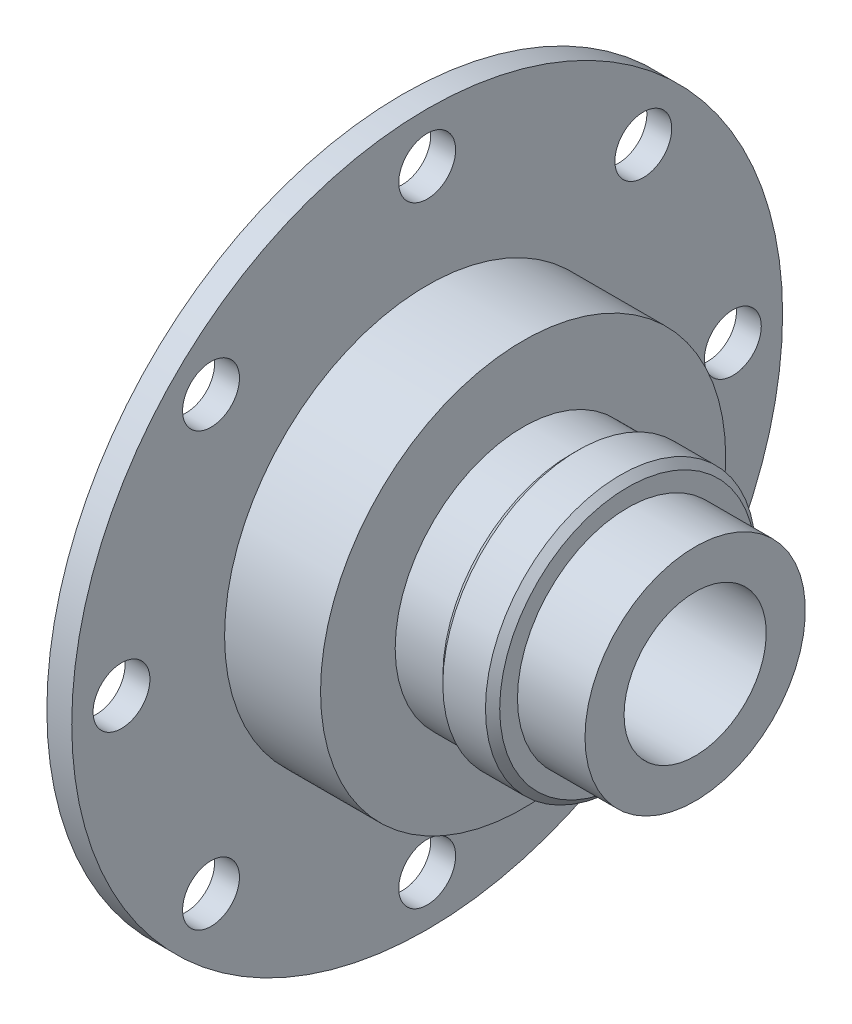
SolidWorks part; units mm, degrees
ref_plane "Alzado" through (0, 0, 0) normal (0, 0, 1) x (1, 0, 0)
ref_plane "Planta" through (0, 0, 0) normal (0, 1, 0) x (1, 0, 0)
ref_plane "Vista lateral" through (0, 0, 0) normal (1, 0, 0) x (0, 0, -1)
sketch "Croquis1" plane through (0, 0, 0) normal (0, 0, 1) x (1, 0, 0)
  line L0 (-60.1026, 0) -> (72.5229, 0) construction
  line L1 (0, 22.25) -> (9.5, 22.25)
  line L2 (9.5, 22.25) -> (9.5, 10)
  line L3 (9.5, 10) -> (41.2, 10)
  line L4 (41.2, 10) -> (41.2, 15.5)
  line L5 (41.2, 15.5) -> (31.7, 15.5)
  line L6 (31.7, 15.5) -> (31.7, 18)
  line L7 (23.7, 18) -> (17, 18)
  line L8 (31.7, 18) -> (31.7, 19)
  line L9 (31.7, 19) -> (23.7, 19)
  line L10 (17, 18) -> (17, 28.5)
  line L11 (17, 28.5) -> (3.5, 28.5)
  line L12 (3.5, 28.5) -> (3.5, 50)
  line L13 (3.5, 50) -> (0, 50)
  line L14 (0, 50) -> (0, 22.25)
  line L15 (23.7, 19) -> (23.7, 18)
  dimension "D1" = 50
  dimension "D2" = 28.5
  dimension "D3" = 22.25
  dimension "D4" = 10
  dimension "D5" = 8
  dimension "D6" = 15.5
  dimension "D7" = 41.2
  dimension "D8" = 9.5
  dimension "D9" = 17
  dimension "D10" = 9.5
  dimension "D11" = 3.5
  dimension "D12" = 1
revolve "Revolución1" add sketch "Croquis1" angle 360 about L0
sketch "Croquis2" plane through (3.5, 0, 0) normal (1, 0, 0) x (0, 0, -1)
  line L0 (0, 43) -> (0, 0) construction
  circle A0 centre (0, 0) radius 43 construction
  circle A1 centre (0, 43) radius 4
  circle A2 centre (30.4056, 30.4056) radius 4
  circle A3 centre (43, 0) radius 4
  circle A4 centre (30.4056, -30.4056) radius 4
  circle A5 centre (0, -43) radius 4
  circle A6 centre (-30.4056, -30.4056) radius 4
  circle A7 centre (-43, 0) radius 4
  circle A8 centre (-30.4056, 30.4056) radius 4
  point P21 (0, 0)
  dimension "D1" = 8
  dimension "D2" = 86
  dimension "D3" = 8
extrude "Cortar-Extruir1" cut sketch "Croquis2" against normal through all
ref_plane "Plano2" through (0, 19, 0) normal (0, 1, 0) x (1, 0, 0)
chamfer "Chaflán1" distance 1 angle 45 2 edges at (23.7, 0, 19) (31.7, 0, 19)
